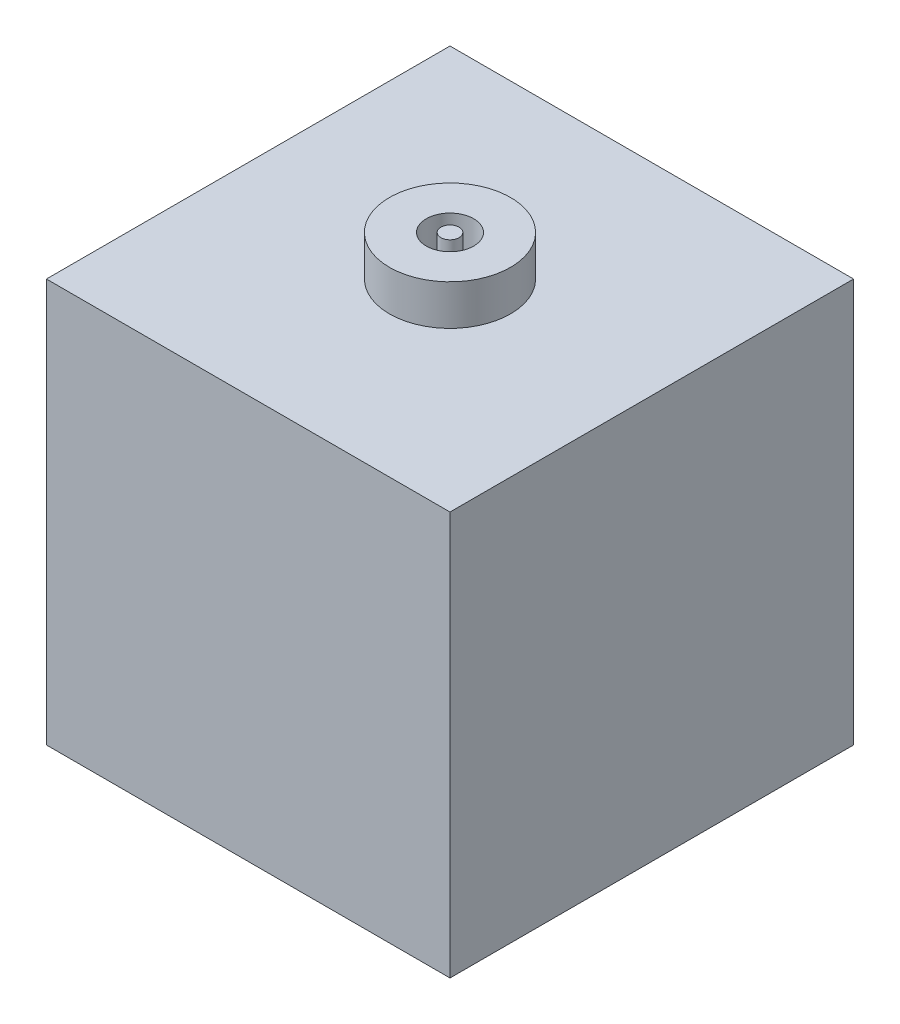
SolidWorks part; units mm, degrees
material "3d打印 35%"
ref_plane "前视基准面" through (0, 0, 0) normal (0, 0, 1) x (1, 0, 0)
ref_plane "上视基准面" through (0, 0, 0) normal (0, 1, 0) x (1, 0, 0)
ref_plane "右视基准面" through (0, 0, 0) normal (1, 0, 0) x (0, 0, -1)
other "Configuration Table"
sketch "草图1" plane through (0, 0, 0) normal (0, 1, 0) x (1, 0, 0)
  line L0 (0, 0) -> (0, 40)
  line L1 (0, 40) -> (40, 40)
  line L2 (40, 40) -> (40, 0)
  line L3 (40, 0) -> (0, 0)
  line L4 (20, 40) -> (20, 0) construction
  circle A0 centre (20, 20) radius 2.35
  circle A1 centre (20, 20) radius 0.9
  circle A2 centre (20, 20) radius 6
  dimension "D1" = 40
  dimension "D2" = 40
extrude "凸台-拉伸1" add sketch "草图1" against normal blind 40 contours L4 L1 L0 L3 A2 | L4 A2 A0 | A2 L4 A0 | L1 L4 A2 L3 L2 | A0 L4 A1 | L4 A0 A1 | L4 A1 | A1 L4 region at (9.4331, 0, -20) region at (30.5669, 0, -20) region at (17.1728, 0, -20) region at (22.8272, 0, -20) region at (18.8969, 0, -20) region at (21.1031, 0, -20) region at (19.618, 0, -20) region at (20.382, 0, -20)
extrude "凸台-拉伸2" add sketch "草图1<3>" along normal blind 4 contours A1 L4 | L4 A1 | L4 A2 A0 | A2 L4 A0 region at (17.1728, 0, -20) region at (22.8272, 0, -20) region at (19.618, 0, -20) region at (20.382, 0, -20)
sketch "草图1<3>" plane through (0, 0, 0) normal (0, 1, 0) x (1, 0, 0) same geometry as "草图1"
